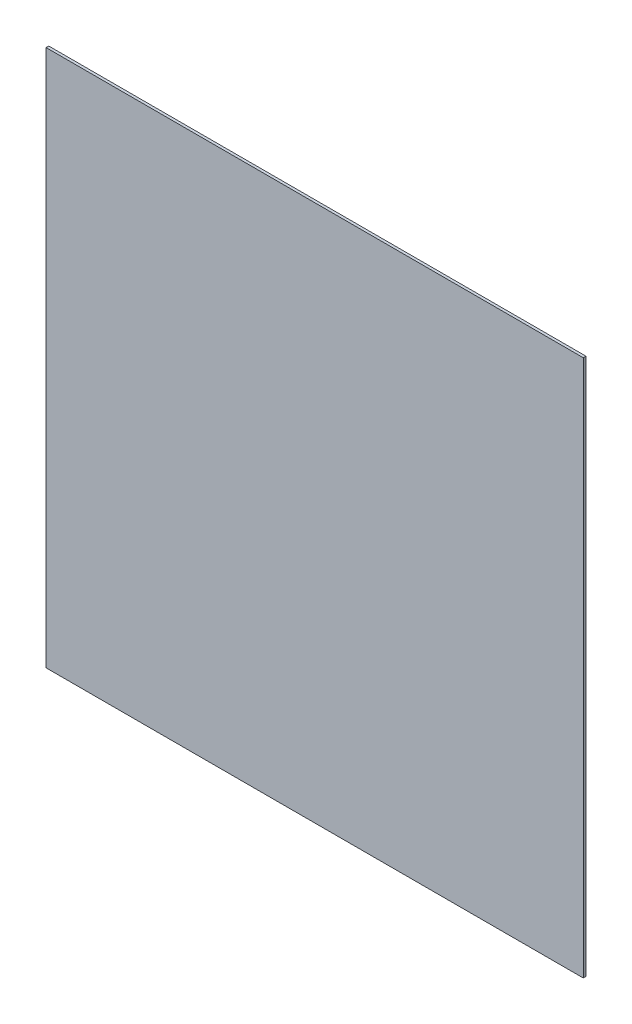
SolidWorks part; units mm, degrees
material "201 Annealed Stainless Steel (SS)"
ref_plane "Front Plane" through (0, 0, 0) normal (0, 0, 1) x (1, 0, 0)
ref_plane "Top Plane" through (0, 0, 0) normal (0, 1, 0) x (1, 0, 0)
ref_plane "Right Plane" through (0, 0, 0) normal (1, 0, 0) x (0, 0, -1)
sketch "Sketch1" plane through (0, 0, 0) normal (0, 0, 1) x (1, 0, 0)
  line L1 (-200, -200) -> (200, -200)
  line L2 (-200, -200) -> (-200, 200)
  line L3 (-200, 200) -> (200, 200)
  line L4 (200, -200) -> (200, 200)
  line L5 (-200, -200) -> (200, 200) construction
  line L6 (-200, 200) -> (200, -200) construction
  point P0 (0, 0)
  dimension "D1" = 400
  dimension "D2" = 400
extrude "Boss-Extrude1" add sketch "Sketch1" along normal blind 2
sketch "Sketch2" [suppressed] plane through (0, 0, 0) normal (0, 0, -1) x (-1, 0, 0)
  line L0 (61, 200) -> (61, -200) construction
  line L1 (-61, 314.7216) -> (-204.3993, 314.7216)
  line L2 (-61, 314.7216) -> (-61, -251.9618)
  line L3 (-61, -251.9618) -> (-204.3993, -251.9618)
  line L4 (-204.3993, 314.7216) -> (-204.3993, -251.9618)
  line L6 (61, 279.3211) -> (244.4765, 279.3211)
  line L7 (61, 279.3211) -> (61, -295.1839)
  line L8 (61, -295.1839) -> (244.4765, -295.1839)
  line L9 (244.4765, 279.3211) -> (244.4765, -295.1839)
  line L10 (-61, -200) -> (-61, -140) construction
extrude "Cut-Extrude1" [suppressed] cut sketch "Sketch2" against normal through all
sketch "Sketch3" [suppressed] plane through (49, 0, 0) normal (1, 0, 0) x (0, 0, -1)
  circle A0 centre (-6.722, 55.3681) radius 5.3835
surface "Surface-Extrude1" [suppressed] sketch "Sketch3"
sketch "Sketch4" [suppressed] plane through (-49, 0, 0) normal (-1, 0, 0) x (0, 0, 1)
  line L1 (2, 80) -> (0, 80) construction
  line L2 (0, -80) -> (0, 80) construction
  point P0 (7.5, 76)
  dimension "D1" = 4
  dimension "D2" = 7.5
ref_axis "Axis1" [suppressed] through (-49, 76, 7.5) along (1, 0, 0)
sketch "Sketch5" [suppressed] plane through (0, 0, 0) normal (0, 0, -1) x (-1, 0, 0)
  line L0 (49, 80) -> (49, -80) construction
  line L1 (-49, 80) -> (49, 80)
  line L2 (-49, 80) -> (-49, 60.2594)
  line L3 (-49, 60.2594) -> (49, 60.2594)
  line L4 (49, 80) -> (49, 60.2594)
extrude "Cut-Extrude2" [suppressed] cut sketch "Sketch5" against normal blind 3
